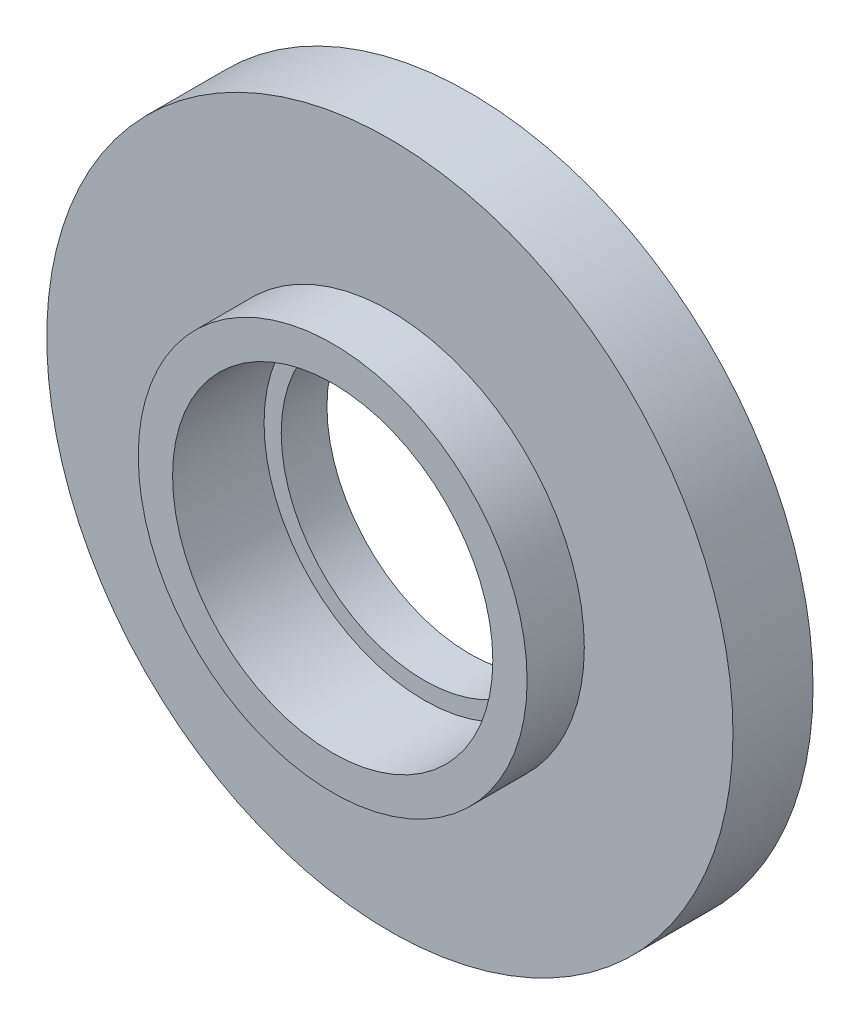
SolidWorks part; units mm, degrees
ref_plane "Front Plane" through (0, 0, 0) normal (0, 0, 1) x (1, 0, 0)
ref_plane "Top Plane" through (0, 0, 0) normal (0, 1, 0) x (1, 0, 0)
ref_plane "Right Plane" through (0, 0, 0) normal (1, 0, 0) x (0, 0, -1)
sketch "Sketch2" plane through (0, 0, 0) normal (0, 1, 0) x (1, 0, 0)
  line L0 (0, 0) -> (-30, 0)
  line L1 (-30, 0) -> (-30, -7)
  line L2 (-30, -7) -> (-17, -7)
  line L3 (-17, -7) -> (-17, -12)
  line L4 (-17, -12) -> (0, -12)
  line L5 (0, -12) -> (0, 0)
  dimension "D1" = 7
  dimension "D2" = 5
  dimension "D3" = 30
  dimension "D4" = 17
revolve "Revolve4" add sketch "Sketch2" angle 360 about L5
sketch "Sketch4" plane through (0, 0, 12) normal (0, 0, 1) x (1, 0, 0)
  circle A0 centre (0, 0) radius 14
  dimension "D1" = 28
extrude "Cut-Extrude1" cut sketch "Sketch4" against normal blind 8
sketch "Sketch5" plane through (0, 0, 0) normal (0, 0, -1) x (-1, 0, 0)
  circle A0 centre (0, 0) radius 12.5
  dimension "D1" = 25
extrude "Cut-Extrude4" cut sketch "Sketch5" against normal blind 8.1
sketch "Sketch7" plane through (0, 0, 0) normal (0, 0, -1) x (-1, 0, 0)
  circle A12 centre (0, 20) radius 2.5
  circle A13 centre (17.3205, 10) radius 2.5
  circle A14 centre (17.3205, -10) radius 2.5
  circle A15 centre (0, -20) radius 2.5
  circle A16 centre (-17.3205, -10) radius 2.5
  circle A17 centre (-17.3205, 10) radius 2.5
  point P14 (0, 0)
  point P15 (0, 0)
  dimension "D1" = 5
  dimension "D2" = 20
  dimension "D3" = 6
extrude "Cut-Extrude5" cut sketch "Sketch7" against normal blind 3
